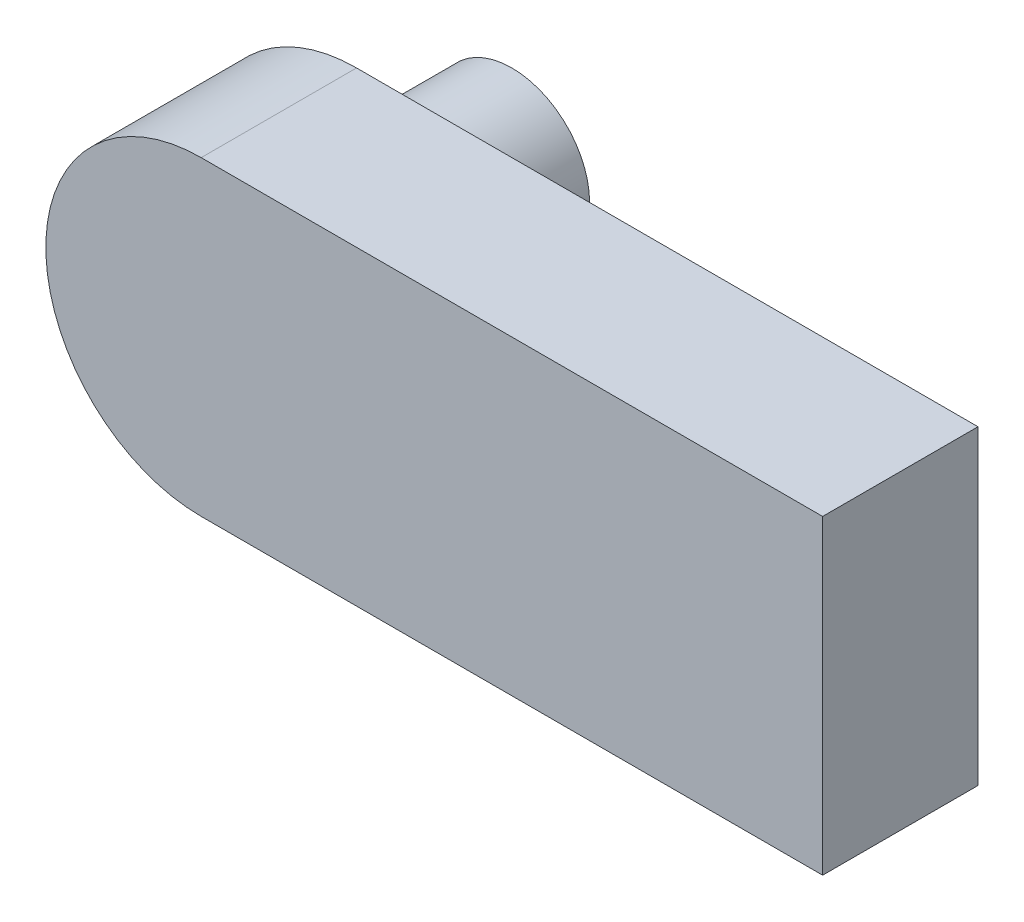
SolidWorks part; units mm, degrees
ref_plane "Piano frontale" through (0, 0, 0) normal (0, 0, 1) x (1, 0, 0)
ref_plane "Piano superiore" through (0, 0, 0) normal (0, 1, 0) x (1, 0, 0)
ref_plane "Piano destro" through (0, 0, 0) normal (1, 0, 0) x (0, 0, -1)
sketch "Schizzo1" plane through (0, 0, 0) normal (0, 0, 1) x (1, 0, 0)
  line L0 (0, 4.5035) -> (-20, 4.5035)
  line L2 (-20, -5.4965) -> (0, -5.4965)
  line L12 (0, 4.5035) -> (0, -5.4965)
  arc A0 (-20, 4.5035) -> (-20, -5.4965) centre (-20, -0.4965) ccw
  dimension "D1" = 10
  dimension "D9" = 20
extrude "Estrusione-Estrusione1" add sketch "Schizzo1" along normal blind 5
sketch "Schizzo2" plane through (0, 0, 0) normal (0, 0, -1) x (-1, 0, 0)
  arc A0 (20, -5.4965) -> (20, 4.5035) centre (20, -0.4965) ccw construction
  arc A1 (20, -5.4965) -> (20, 4.5035) centre (20, -0.4965) ccw construction
  circle A2 centre (20, -0.4965) radius 2.5
extrude "Estrusione-Estrusione2" add sketch "Schizzo2" along normal blind 5 contours A2
